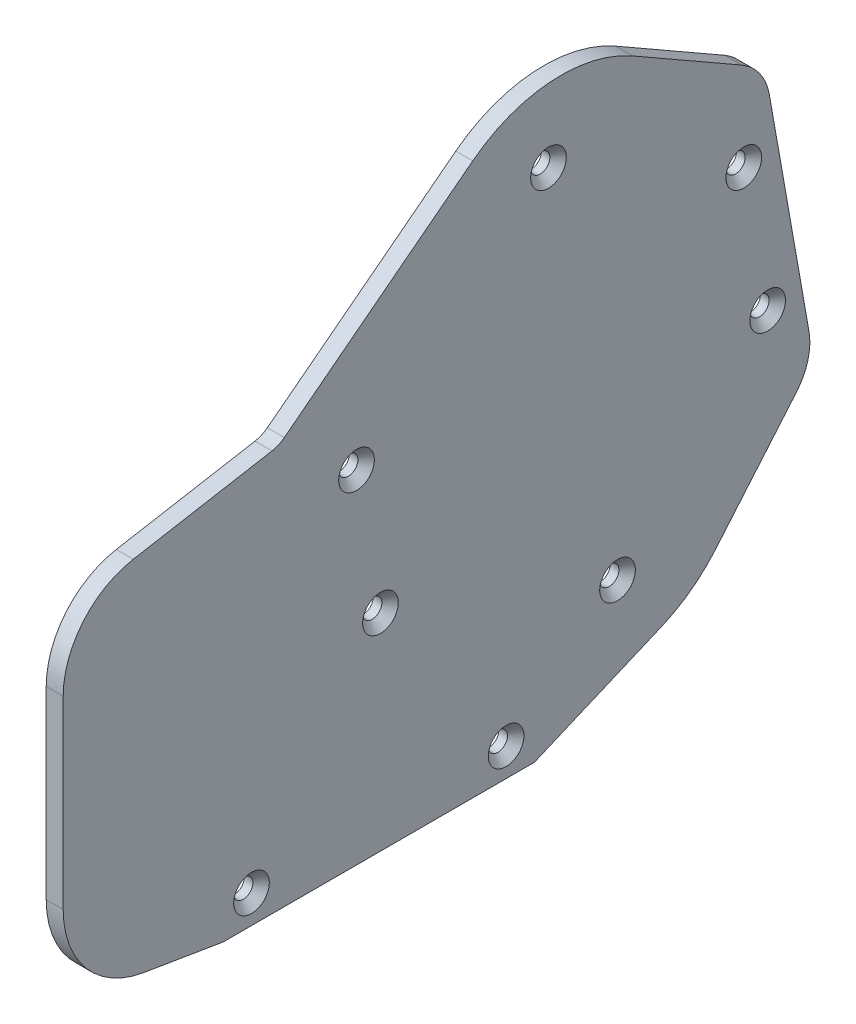
SolidWorks part; units mm, degrees
material "Thornel VCB-20 Carbon Cloth"
ref_plane "Front Plane" through (0, 0, 0) normal (0, 0, 1) x (1, 0, 0)
ref_plane "Top Plane" through (0, 0, 0) normal (0, 1, 0) x (1, 0, 0)
ref_plane "Right Plane" through (0, 0, 0) normal (1, 0, 0) x (0, 0, -1)
ref_plane "Plane1" through (29, 0, 0) normal (1, 0, 0) x (0, 0, -1)
sketch "Sketch2" plane through (29, 0, 0) normal (1, 0, 0) x (0, 0, -1)
  line L4 (-16.6915, 108.8163) -> (16.6101, 134.5066)
  line L6 (69.0263, 118.4582) -> (76.0353, 78.7081)
  line L8 (-27.5, 37) -> (27.5, 37)
  line L9 (27.5, 37) -> (49.9564, 46.5241)
  line L10 (68.8961, 119.1968) -> (76.1656, 77.9695) construction
  line L11 (64.1472, 125.3998) -> (44.8568, 136.4454)
  line L12 (59.4754, 53.5392) -> (73.8247, 70.5164)
  line L13 (-27.5, 37) -> (-41.5712, 39.3381)
  line L14 (-18.8773, 107.8511) -> (-43.3893, 103.529)
  line L15 (-55.7846, 88.7569) -> (-55.7846, 56.1081)
  line L16 (-42.1957, 104.2472) -> (-19.5451, 108.2411) construction
  circle A0 centre (40, 70) radius 22.5 construction
  circle A4 centre (-22.5, 42) radius 3 construction
  circle A5 centre (22.5, 42) radius 3 construction
  circle A6 centre (32.1858, 114.3163) radius 22.5 construction
  circle A7 centre (40, 70) radius 22.5 construction
  circle A8 centre (32.1858, 114.3163) radius 22.5 construction
  arc A12 (49.9564, 46.5241) -> (59.4754, 53.5392) centre (40, 70) ccw
  arc A13 (44.8568, 136.4454) -> (16.6101, 134.5066) centre (32.1858, 114.3163) ccw
  arc A14 (69.0263, 118.4582) -> (64.1472, 125.3998) centre (59.1782, 116.7217) ccw
  arc A15 (76.0353, 78.7081) -> (73.8247, 70.5164) centre (66.1872, 76.9716) cw
  arc A16 (-55.7846, 56.1081) -> (-41.5712, 39.3381) centre (-38.7846, 56.1081) ccw
  circle A17 centre (-38.7846, 56.1081) radius 14 construction
  arc A19 (-16.6915, 108.8163) -> (-18.8773, 107.8511) centre (-19.7456, 112.7751) cw
  arc A20 (-43.3893, 103.529) -> (-55.7846, 88.7569) centre (-40.7846, 88.7569) ccw
  arc A21 (-15.3585, 110.4119) -> (-19.7366, 103.5685) centre (-13.8278, 104.6104) ccw construction
  point P36 (-19.5139, 106.5256)
  point P50 (-16.8202, 108.755)
  point P51 (-41.5712, 89.4025)
  dimension "D1" = 6
  dimension "D2" = 3
  dimension "D3" = 3
  dimension "D5" = 5
  dimension "D6" = 15
  dimension "D7" = 10
  dimension "D4" = 0.5
extrude "Boss-Extrude1" add sketch "Sketch2" along normal blind 3 contours A13 L4 L8 L9 A12 region at (29, 82.4064, -11.6288)
hole_wizard "CSK for M3 Flat Head Machine Screw1" positions "Sketch3" profile "Sketch4" countersink size "M3" standard "ANSI Metric" end condition through all
sketch "Sketch3" plane through (32, 0, 0) normal (1, 0, 0) x (0, 0, -1)
  point P0 (64.5066, 109.5379)
  point P3 (68.7373, 85.5447)
  point P6 (-3.9375, 97.4693)
  point P9 (0.2931, 73.4761)
  point P12 (42.1966, 57.5422)
  point P15 (29.9892, 126.7742)
  point P19 (-22.5, 42)
  point P22 (22.5, 42)
sketch "Sketch4" plane through (32, 109.5379, -64.5066) normal (0, 1, 0) x (0, 0, -1)
  line L0 (0, 0) -> (0, 3)
  line L1 (0, 3) -> (1.7, 3)
  line L2 (1.7, 3) -> (1.7, 1.45)
  line L3 (1.7, 1.45) -> (3.15, 0)
  line L5 (3.15, 0) -> (0, 0)
  line L6 (-1.7, 1.45) -> (-3.15, 0) construction
  line L11 (0, -6.35) -> (0, 107.95) construction
  dimension "Thru Hole Dia." = 3.4
  dimension "Thru Hole Depth" = 3
  dimension "Near C'Sink Dia." = 6.3
  dimension "Near C'Sink Angle" = 90
